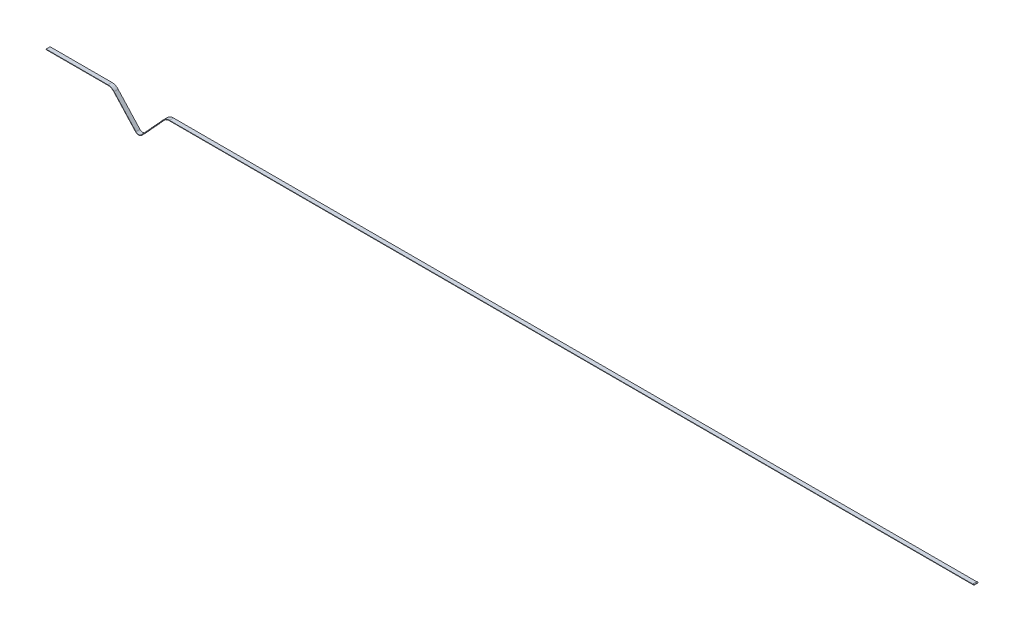
SolidWorks part; units mm, degrees
material "BUTYL"
ref_plane "Front Plane" through (0, 0, 0) normal (0, 0, 1) x (1, 0, 0)
ref_plane "Top Plane" through (0, 0, 0) normal (0, 1, 0) x (1, 0, 0)
ref_plane "Right Plane" through (0, 0, 0) normal (1, 0, 0) x (0, 0, -1)
sketch "Sketch1" plane through (0, 0, 0) normal (1, 0, 0) x (0, 0, -1)
  line L1 (0, 0) -> (6, 0)
  line L2 (0, 0) -> (0, 0.63)
  line L3 (0, 0.63) -> (6, 0.63)
  line L4 (6, 0) -> (6, 0.63)
  dimension "D1" = 0.63
  dimension "D2" = 6
sketch "Sketch2" plane through (0, 0, 0) normal (0, 0, 1) x (1, 0, 0)
  line L0 (0, 0) -> (-1189.1112, 0)
  line L1 (-1197.9302, -3.886) -> (-1230.172, -39.1468)
  line L2 (-1239.1903, -39.1468) -> (-1271.4322, -3.886)
  line L3 (-1280.2512, 0) -> (-1371.6, 0)
  arc A0 (-1189.1112, 0) -> (-1197.9302, -3.886) centre (-1189.1112, -11.95) ccw
  arc A1 (-1230.172, -39.1468) -> (-1239.1903, -39.1468) centre (-1234.6812, -35.0237) cw
  arc A2 (-1271.4322, -3.886) -> (-1280.2512, 0) centre (-1280.2512, -11.95) ccw
  circle A3 centre (-1189.1112, -11.95) radius 11.95 construction
  circle A4 centre (-1280.2512, -11.95) radius 11.95 construction
  circle A5 centre (-1234.6812, -35.0237) radius 6.11 construction
  dimension "D1" = 6.11
  dimension "D4" = 1371.6
sweep "Sweep1" add profiles "Sketch1" path "Sketch2"
sketch "Sketch3" plane through (0, 0, 0) normal (0, 0, 1) x (1, 0, 0)
  line L0 (0, 0.63) -> (-1189.1112, 0.63) construction
  line L1 (-1.5, 0.63) -> (-1.5, 0)
  line L2 (0, 0) -> (-1189.1112, 0) construction
  line L3 (-1.5, 0) -> (0, 0)
  line L4 (0, 0) -> (0, 0.63)
  arc A1 (0, 0.63) -> (-1.5, 0.63) centre (-0.75, 0.63) ccw
  dimension "D1" = 0.75
extrude "Boss-Extrude1" add sketch "Sketch3" against normal through all
pattern_curve "CrvPattern1" [suppressed] of bodies 102 driven by "Sketch2" parameters "D1"=2000, "D3"=2, "D2"=1, "D4"=10
